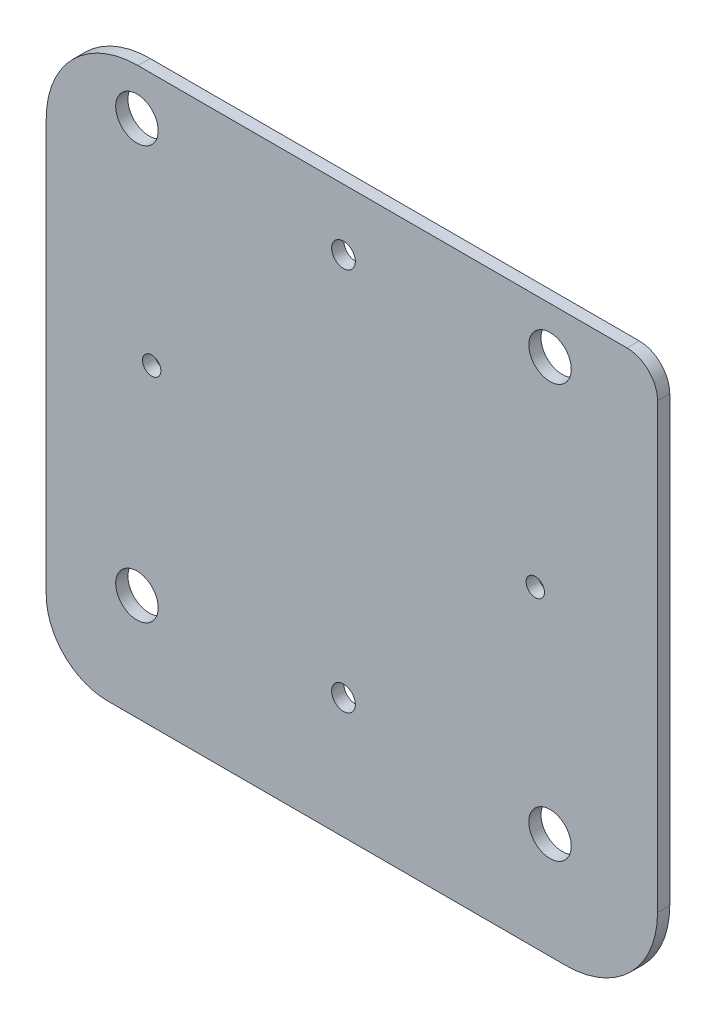
SolidWorks part; units mm, degrees
material "FR4_stuffedProtoboard"
ref_plane "Front Plane" through (0, 0, 0) normal (0, 0, 1) x (1, 0, 0)
ref_plane "Top Plane" through (0, 0, 0) normal (0, 1, 0) x (1, 0, 0)
ref_plane "Right Plane" through (0, 0, 0) normal (1, 0, 0) x (0, 0, -1)
sketch "Imported DXF" plane through (0, 0, 0) normal (0, 0, 1) x (1, 0, 0)
  line L0 (-21.6929, 33.1) -> (40.8929, 33.1)
  line L1 (41.2464, 32.9535) -> (43.9536, 30.2464)
  line L2 (44.1, 29.8929) -> (44.1, -26.6929)
  line L3 (43.9535, -27.0465) -> (30.2464, -40.7536)
  line L4 (29.8929, -40.9) -> (-30.6929, -40.9)
  line L5 (-31.0465, -40.7536) -> (-38.7536, -33.0464)
  line L6 (-38.9001, -32.6946) -> (-38.9148, 15.8797)
  line L7 (-38.7685, 16.2316) -> (-22.0464, 32.9536)
  line L8 (34.175, 6.26) -> (32.925, 6.26)
  line L9 (32.925, 6.26) -> (32.925, 8.26)
  line L10 (32.925, 8.26) -> (34.175, 8.26)
  line L11 (34.175, 8.26) -> (34.175, 6.26)
  line L12 (5.75, 8.485) -> (5.75, 9.735)
  line L13 (5.75, 9.735) -> (7.75, 9.735)
  line L14 (7.75, 9.735) -> (7.75, 8.485)
  line L15 (7.75, 8.485) -> (5.75, 8.485)
  line L16 (-4.91, -8.495) -> (-4.91, -9.745)
  line L17 (-4.91, -9.745) -> (-6.91, -9.745)
  line L18 (-6.91, -9.745) -> (-6.91, -8.495)
  line L19 (-6.91, -8.495) -> (-4.91, -8.495)
  line L20 (39.91, -3.075) -> (32.29, -3.075)
  line L21 (32.29, 3.275) -> (39.91, 3.275)
  line L22 (32.671, -3.075) -> (32.29, -3.075)
  line L23 (32.29, -3.075) -> (32.29, 3.275)
  line L24 (32.29, 3.275) -> (32.671, 3.275)
  line L25 (39.529, -3.075) -> (39.91, -3.075)
  line L26 (39.91, -3.075) -> (39.91, 3.275)
  line L27 (39.91, 3.275) -> (39.529, 3.275)
  line L28 (-3.81, 15.275) -> (3.81, 15.275)
  line L29 (3.81, 8.925) -> (-3.81, 8.925)
  line L30 (3.429, 15.275) -> (3.81, 15.275)
  line L31 (3.81, 15.275) -> (3.81, 8.925)
  line L32 (3.81, 8.925) -> (3.429, 8.925)
  line L33 (-3.429, 15.275) -> (-3.81, 15.275)
  line L34 (-3.81, 15.275) -> (-3.81, 8.925)
  line L35 (-3.81, 8.925) -> (-3.429, 8.925)
  line L36 (3.81, -15.275) -> (-3.81, -15.275)
  line L37 (-3.81, -8.925) -> (3.81, -8.925)
  line L38 (-3.429, -15.275) -> (-3.81, -15.275)
  line L39 (-3.81, -15.275) -> (-3.81, -8.925)
  line L40 (-3.81, -8.925) -> (-3.429, -8.925)
  line L41 (3.429, -15.275) -> (3.81, -15.275)
  line L42 (3.81, -15.275) -> (3.81, -8.925)
  line L43 (3.81, -8.925) -> (3.429, -8.925)
  line L44 (0, 37.7984) -> (0, -46.2816) construction
  line L45 (-65.7891, 0) -> (80.4964, 0) construction
  arc A0 (41.2464, 32.9535) -> (40.8929, 33.1) centre (40.8929, 32.6) ccw
  arc A1 (44.1, 29.8929) -> (43.9535, 30.2464) centre (43.6, 29.8929) ccw
  arc A2 (43.9535, -27.0465) -> (44.1, -26.6929) centre (43.6, -26.6929) ccw
  arc A3 (29.8929, -40.9) -> (30.2464, -40.7536) centre (29.8929, -40.4) ccw
  arc A4 (-31.0465, -40.7536) -> (-30.6929, -40.9) centre (-30.6929, -40.4) ccw
  arc A5 (-38.9001, -32.6946) -> (-38.7537, -33.0464) centre (-38.4001, -32.6928) ccw
  arc A6 (-38.7685, 16.2316) -> (-38.9149, 15.8796) centre (-38.4155, 15.8783) ccw
  arc A7 (-21.6929, 33.1) -> (-22.0465, 32.9535) centre (-21.6929, 32.6) ccw
  circle A8 centre (-25.1, 0) radius 1.2
  circle A9 centre (25.1, 0) radius 1.2
  circle A10 centre (0, 25.1) radius 1.55
  circle A11 centre (0, -25.1) radius 1.55
  circle A12 centre (40.481, 2.989) radius 0.254
  circle A13 centre (-4.381, 9.211) radius 0.254
  circle A14 centre (4.381, -9.211) radius 0.254
  point P20 (0, 0)
  point P40 (33.55, 7.26)
  point P45 (6.75, 9.11)
  point P50 (-5.91, -9.12)
  point P55 (38.1, 26.1)
  point P56 (23.4, 23.4)
  point P57 (-23.4, 23.4)
  point P58 (-23.4, -23.4)
  point P59 (23.4, -23.4)
  point P60 (36.1, 0.1)
  point P71 (0, 12.1)
  point P82 (0, -12.1)
  dimension "D1" = 3.1
sketch "New Imported DXF" plane through (0, 0, 0) normal (0, 0, 1) x (1, 0, 0)
  line L0 (41.1, 29.1) -> (41.1, -28.9)
  line L1 (29.1, -40.9) -> (-30.9, -40.9)
  line L2 (-38.9, -32.9) -> (-38.9, 21.1)
  line L3 (-26.9, 33.1) -> (37.1, 33.1)
  line L4 (-27, -27) -> (27, 27) construction
  line L5 (27, -27) -> (-27, 27) construction
  line L6 (-25.1, 0) -> (25.1, 0) construction
  line L7 (0, 25.1) -> (0, -25.1) construction
  arc A0 (41.1, 29.1) -> (37.1, 33.1) centre (37.1, 29.1) ccw
  arc A1 (29.1, -40.9) -> (41.1, -28.9) centre (29.1, -28.9) ccw
  arc A2 (-38.9, -32.9) -> (-30.9, -40.9) centre (-30.9, -32.9) ccw
  arc A3 (-26.9, 33.1) -> (-38.9, 21.1) centre (-26.9, 21.1) ccw
  circle A4 centre (-25.1, 0) radius 1.2
  circle A5 centre (25.1, 0) radius 1.2
  circle A6 centre (0, 25.1) radius 1.55
  circle A7 centre (0, -25.1) radius 1.55
  circle A8 centre (27, 27) radius 2.75
  circle A9 centre (-27, 27) radius 2.75
  circle A10 centre (27, -27) radius 2.75
  circle A11 centre (-27, -27) radius 2.75
  point P28 (0, 0)
  dimension "D5" = 4
  dimension "D6" = 12
  dimension "D7" = 8
  dimension "D8" = 12
  dimension "D13" = 5.5
  dimension "D20" = 2.4
  dimension "D21" = 3.1
  dimension "D1" = 54
  dimension "D2" = 58
  dimension "D3" = 64
  dimension "D4" = 60
  dimension "D9" = 38.9
  dimension "D10" = 41.1
  dimension "D11" = 40.9
  dimension "D12" = 33.1
  dimension "D14" = 27
  dimension "D15" = 27
  dimension "D16" = 27
  dimension "D17" = 27
  dimension "D18" = 13.8
sketch "Outline" plane through (0, 0, 0) normal (0, 0, 1) x (1, 0, 0)
  line L9 (-38.9, 21.1) -> (-38.9, -32.9)
  line L10 (-30.9, -40.9) -> (29.1, -40.9)
  line L11 (41.1, -28.9) -> (41.1, 29.1)
  line L12 (-26.9, 33.1) -> (37.1, 33.1) construction
  line L17 (-26.9, 33.1) -> (37.1, 33.1)
  arc A0 (-38.9, 21.1) -> (-26.9, 33.1) centre (-26.9, 21.1) cw
  arc A1 (-26.9, 33.1) -> (-38.9, 21.1) centre (-26.9, 21.1) ccw construction
  arc A2 (41.1, 29.1) -> (37.1, 33.1) centre (37.1, 29.1) ccw
  arc A4 (41.1, -28.9) -> (29.1, -40.9) centre (29.1, -28.9) cw
  arc A5 (-38.9, -32.9) -> (-30.9, -40.9) centre (-30.9, -32.9) ccw
  arc A6 (-38.9, -32.9) -> (-30.9, -40.9) centre (-30.9, -32.9) ccw construction
  arc A7 (41.1, 29.1) -> (37.1, 33.1) centre (37.1, 29.1) ccw construction
extrude "Boss-Extrude1" add sketch "Outline" along normal blind 1.6
sketch "Connector locations" plane through (0, 0, 1.6) normal (0, 0, 1) x (1, 0, 0)
  line L1 (24.5314, 22.2686) -> (22.2686, 24.5314)
  line L2 (38.1, 27.7) -> (38.1, 24.5)
  line L3 (22.2686, -24.5314) -> (24.5314, -22.2686)
  line L4 (0, 0) -> (23.4, 23.4) construction
  line L5 (-24.5314, -22.2686) -> (-22.2686, -24.5314)
  line L6 (-22.2686, 24.5314) -> (-24.5314, 22.2686)
  line L9 (-21.6929, 33.1) -> (40.8929, 33.1) construction
  line L10 (-65.7891, 0) -> (80.4964, 0) construction
  point P13 (38.1, 26.1)
  dimension "D1" = 45
  dimension "D3" = 45
  dimension "D4" = 33.0926
  dimension "D6" = 3.2
sketch "Sketch3" plane through (0, 0, 1.6) normal (0, 0, 1) x (1, 0, 0)
  circle A0 centre (0, 25.1) radius 1.55
  circle A1 centre (25.1, 0) radius 1.2
  circle A2 centre (0, -25.1) radius 1.55
  circle A3 centre (-25.1, 0) radius 1.2
  circle A4 centre (25.1, 0) radius 1.2 construction
  circle A5 centre (0, 25.1) radius 1.55 construction
  circle A6 centre (-25.1, 0) radius 1.2 construction
  circle A7 centre (0, -25.1) radius 1.55 construction
extrude "Cut-Extrude3" cut sketch "Sketch3" against normal up to next
sketch "Press Fit Nut Locations" plane through (0, 0, 1.6) normal (0, 0, 1) x (1, 0, 0)
  circle A0 centre (-27.0307, 27.0307) radius 2.78 construction
  circle A1 centre (27.0307, 27.0307) radius 2.78 construction
  circle A2 centre (-27.0307, -27.0307) radius 2.78 construction
  circle A3 centre (27.0307, -27.0307) radius 2.78 construction
  circle A4 centre (-27.0307, 27.0307) radius 2.78
  circle A5 centre (27.0307, 27.0307) radius 2.78
  circle A6 centre (-27.0307, -27.0307) radius 2.78
  circle A7 centre (27.0307, -27.0307) radius 2.78
sketch "Frame Boss Lines" plane through (0, 0, 1.6) normal (0, 0, 1) x (1, 0, 0)
  line L0 (-41.5, 37.8828) -> (-41.5, -46.4929)
  line L1 (-41.5, -37) -> (-41.5, -41.5) construction
  line L2 (41.5, -37) -> (41.5, -41.5) construction
  line L3 (-41.5, -37) -> (-41.5, -41.5) construction
  line L4 (41.5, -37) -> (41.5, -41.5) construction
  line L7 (41.5, 37.8828) -> (41.5, -46.4929)
extrude "Cut-Extrude4" cut sketch "Press Fit Nut Locations" against normal up to next
